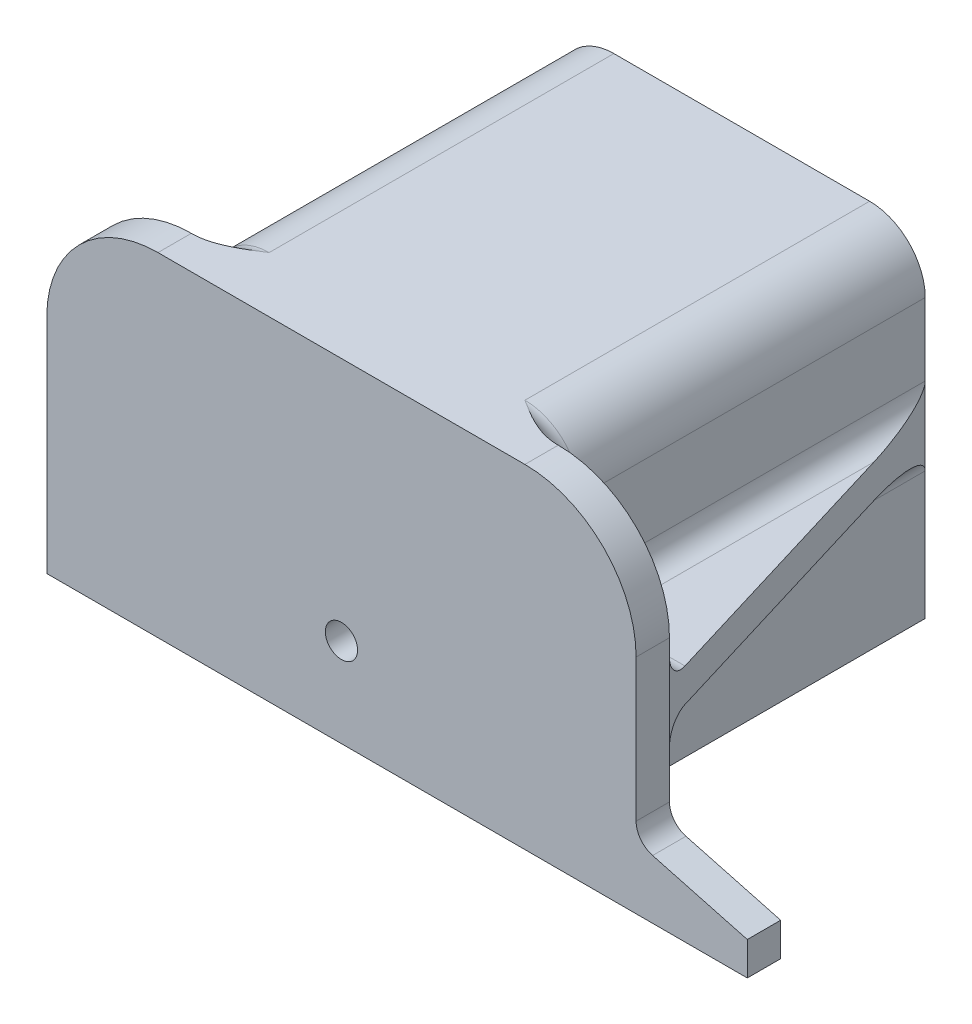
SolidWorks part; units mm, degrees
material "ABS"
ref_plane "Front Plane" through (0, 0, 0) normal (0, 0, 1) x (1, 0, 0)
ref_plane "Top Plane" through (0, 0, 0) normal (0, 1, 0) x (1, 0, 0)
ref_plane "Right Plane" through (0, 0, 0) normal (1, 0, 0) x (0, 0, -1)
sketch "Sketch1" plane through (0, 0, 0) normal (0, 1, 0) x (1, 0, 0)
  line L0 (0, 0) -> (0, -6) construction
  line L1 (13.5, 0) -> (-13.5, 0)
  line L2 (-13.5, 0) -> (-13.5, 30)
  line L3 (-13.5, 30) -> (-16.5, 30)
  line L4 (-26.5, -6) -> (-26.5, -3)
  line L5 (-26.5, -6) -> (26.5, -6)
  line L7 (-16.5, -3) -> (-16.5, 30)
  line L8 (-26.5, -3) -> (-16.5, -3)
  line L9 (26.5, -3) -> (16.5, -3)
  line L10 (16.5, -3) -> (16.5, 30)
  line L12 (26.5, -6) -> (26.5, -3)
  line L13 (13.5, 30) -> (16.5, 30)
  line L14 (13.5, 0) -> (13.5, 30)
  dimension "D1" = 13.5
  dimension "D2" = 30
  dimension "D3" = 6
  dimension "D4" = 3
  dimension "D5" = 10
  dimension "D6" = 3
extrude "Boss-Extrude1" add sketch "Sketch1" along normal mid plane 30
sketch "Sketch2" plane through (0, 0, 0) normal (0, 1, 0) x (1, 0, 0)
  line L0 (16.5, 30) -> (16.5, -3)
  line L1 (16.5, -3) -> (26.5, -3)
  line L2 (26.5, -3) -> (16.5, 30)
extrude "Boss-Extrude2" add sketch "Sketch2" along normal mid plane 3
mirror "Mirror1" about plane through (0, 0, 0) normal (1, 0, 0) of "Boss-Extrude2"
sketch "Sketch3" plane through (0, 0, 0) normal (0, 0, -1) x (-1, 0, 0)
  line L0 (0, 0) -> (0, -7) construction
  line L1 (0, -7) -> (0, -15) construction
  line L2 (-13.5, -15) -> (13.5, -15) construction
  circle A0 centre (0, -7) radius 1.45
  dimension "D2" = 2.9
  dimension "D1" = 8
extrude "Cut-Extrude1" cut sketch "Sketch3" against normal through all
fillet "Fillet1" radius 10 2 edges at (26.5, 15, 4.5) (-26.5, 15, 4.5)
sketch "Sketch4" plane through (0, 0, 0) normal (0, 0, -1) x (-1, 0, 0)
  circle A0 centre (0, -7) radius 5
  dimension "10mm" = 10
extrude "Cut-Extrude4" cut sketch "Sketch4" against normal blind 2
fillet "Fillet2" radius 0.5 1 edges at (-5, -7, 2)
sketch "Sketch5" plane through (0, 0, 0) normal (0, 0, -1) x (-1, 0, 0)
  line L0 (-13.5, 15) -> (-13.5, -15) construction
  line L3 (13.5, 15) -> (-13.5, 15)
  line L7 (13.5, 15) -> (13.5, 12)
  line L8 (13.5, 12) -> (-13.5, 12)
  line L9 (-13.5, 15) -> (-13.5, 12)
  dimension "D1" = 3
extrude "Boss-Extrude3" add sketch "Sketch5" along normal up to surface (30 mm away) up to face at (-15.5, 0, -30)
sketch "Sketch6" plane through (26.5, 0, 0) normal (1, 0, 0) x (0, 0, -1)
  line L0 (-6, -15) -> (-3, -15)
  line L1 (-3, -15) -> (-3, -12)
  line L2 (-3, -1.5) -> (-3, -15) construction
  line L3 (-3, -12) -> (-6, -12)
  line L4 (-6, 5) -> (-6, -15) construction
  line L5 (-6, -12) -> (-6, -15)
extrude "Boss-Extrude4" add sketch "Sketch6" along normal blind 10
chamfer "Chamfer1" distance 10 angle 15 1 edges at (26.5, -12, 4.5) first distance on face at (31.5, -12, 4.5)
fillet "Fillet3" radius 5 4 edges at (-13.5, 12, -15) (13.5, 12, -15) (-16.5, 15, -13.5) (16.5, 15, -13.5)
fillet "Fillet4" radius 2 15 edges at (-15.0355, 13.5355, 3) (15.0355, 13.5355, 3) (-16.5, -1.5, -13.5) (-21.5, -1.5, 3) (-21.5, 1.5, 3) (-16.5, 1.5, -13.5) (-16.5, 5.75, 3) (-16.5, -8.25, 3) (16.5, 5.75, 3) (16.5, -8.25, 3) (16.5, -1.5, -13.5) (21.5, -1.5, 3) (21.5, 1.5, 3) (16.5, 1.5, -13.5) (26.5, -9.3205, 4.5)
